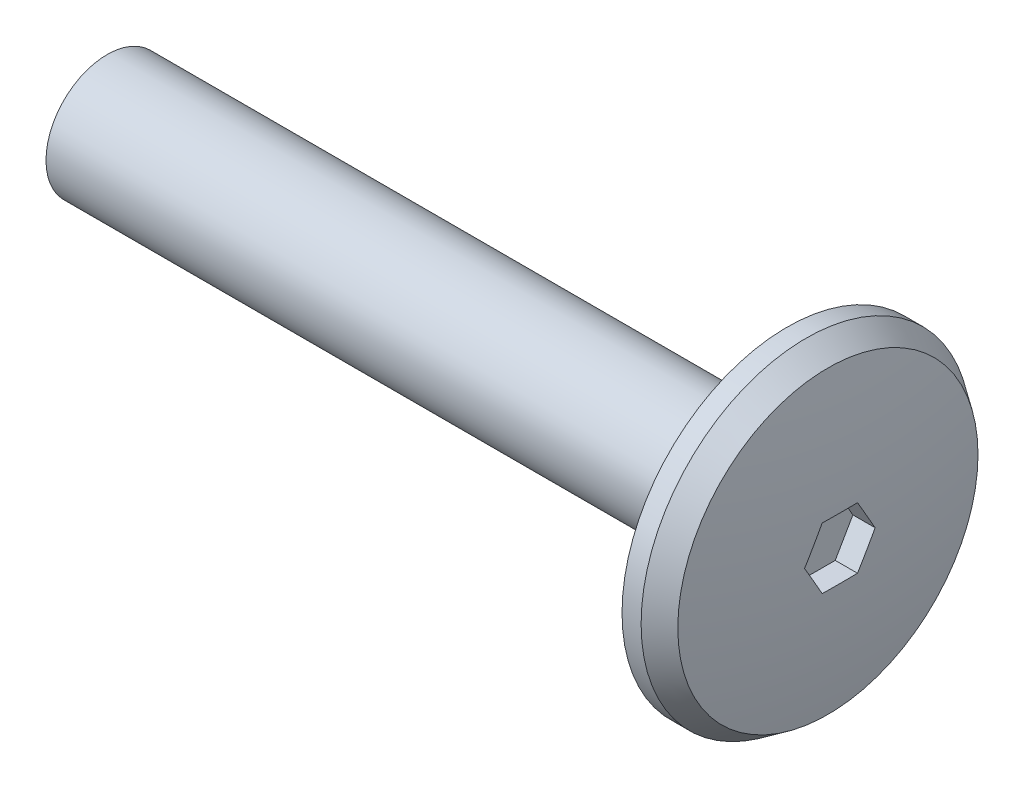
SolidWorks part; units mm, degrees
material "10B21"
ref_plane "Front Plane" through (0, 0, 0) normal (0, 0, 1) x (1, 0, 0)
ref_plane "Top Plane" through (0, 0, 0) normal (0, 1, 0) x (1, 0, 0)
ref_plane "Right Plane" through (0, 0, 0) normal (1, 0, 0) x (0, 0, -1)
sketch "Sketch1" plane through (0, 0, 0) normal (0, 0, 1) x (1, 0, 0)
  line L0 (0, 0) -> (48, 0)
  line L1 (47, 10.8) -> (44, 10.8)
  line L2 (44, 10.8) -> (44, 4)
  line L3 (44, 4) -> (0, 4)
  line L4 (0, 4) -> (0, 0)
  arc A0 (48, 0) -> (47, 10.8) centre (-10.82, 0) ccw
  dimension "D1" = 44
  dimension "D6" = 58.82
  dimension "D2" = 4
  dimension "D3" = 4
  dimension "D4" = 10.8
  dimension "D5" = 3
revolve "Revolve1" add sketch "Sketch1" angle 360 about L0
hole_wizard "M6 Tapped Hole1" positions "Sketch5" profile "Sketch6" tap size "M6" standard "ISO"
sketch "Sketch5" plane through (0, 0, 0) normal (-1, 0, 0) x (0, 0, 1)
  point P0 (0, 0)
sketch "Sketch6" plane through (0, 0, 0) normal (0, 1, 0) x (0, 0, 1)
  line L0 (0, 0) -> (0, 21.5022)
  line L1 (0, 21.5022) -> (2.5, 20)
  line L2 (2.5, 20) -> (2.5, 0)
  line L5 (2.5, 0) -> (0, 0)
  line L10 (0, 21.5022) -> (-2.5, 20) construction
  line L11 (0, -6.35) -> (0, 107.95) construction
  dimension "Tap Drill Dia." = 5
  dimension "Tap Drill Depth" = 20
  dimension "Drill Angle" = 118
cosmetic thread "Hole Thread1"
chamfer "Chamfer1" distance 1 angle 45 1 edges at (47, 0, 10.8) first distance on face at (47, 0, 10.8)
sketch "Sketch7" plane through (0, 0, 0) normal (-1, 0, 0) x (0, 0, 1)
  line L0 (0, 0) -> (15.1977, 0) construction
  line L1 (-1.9365, 3.5) -> (1.9365, 3.5)
  line L2 (-1.9365, -3.5) -> (1.9365, -3.5)
  arc A0 (-1.9365, -3.5) -> (1.9365, -3.5) centre (0, 0) ccw
  circle A1 centre (0, 0) radius 4
  arc A2 (1.9365, 3.5) -> (-1.9365, 3.5) centre (0, 0) ccw
  dimension "D1" = 0
  dimension "D2" = 7
sketch "Sketch8" plane through (44, 0, 0) normal (-1, 0, 0) x (0, 0, 1)
  circle A0 centre (0, 0) radius 6
  circle A1 centre (0, 0) radius 10.8
  circle A2 centre (0, 0) radius 10.8
  dimension "D2" = 12
  dimension "D1" = 0
extrude "Cut-Extrude2" cut sketch "Sketch8" against normal blind 0.5
chamfer "Chamfer2" distance 0.5 angle 45 1 edges at (44, 0, 6)
sketch "Sketch9" plane through (44.5, 0, 0) normal (-1, 0, 0) x (0, 0, 1)
  line L1 (1.1547, -2) -> (2.3094, 0)
  line L2 (2.3094, 0) -> (1.1547, 2)
  line L3 (1.1547, 2) -> (-1.1547, 2)
  line L4 (-1.1547, 2) -> (-2.3094, 0)
  line L5 (-2.3094, 0) -> (-1.1547, -2)
  line L6 (-1.1547, -2) -> (1.1547, -2)
  circle A0 centre (0, 0) radius 2 construction
  dimension "D1" = 4
extrude "Cut-Extrude3" cut sketch "Sketch9" against normal through all from offset 2 offset against normal yes
